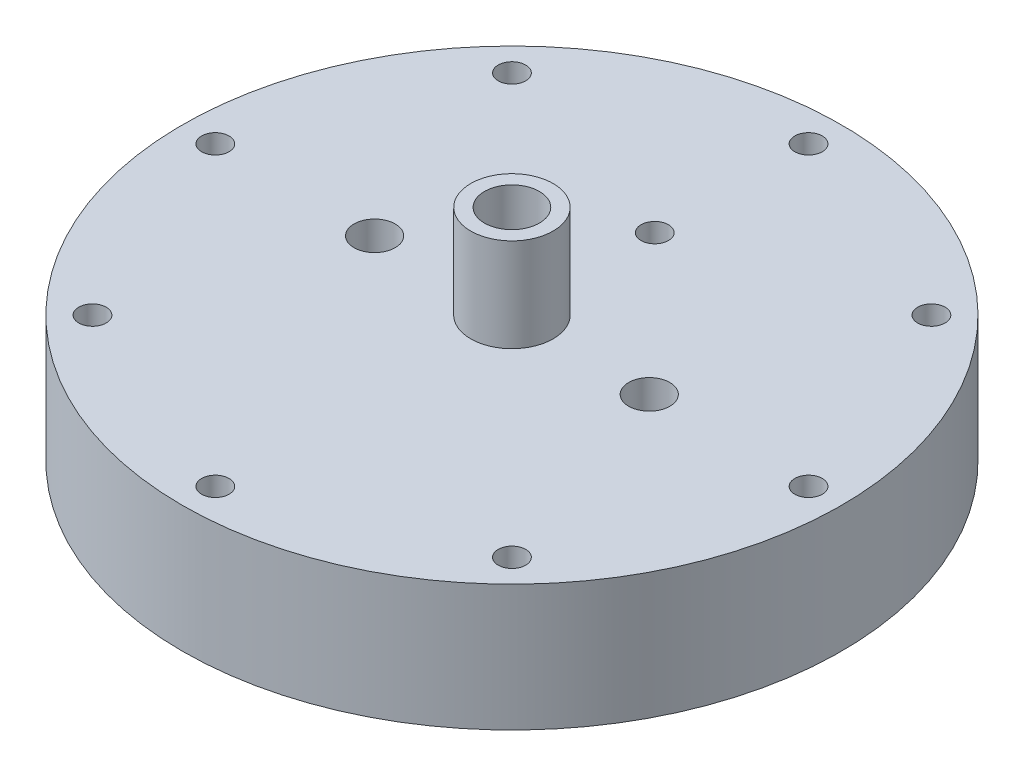
SolidWorks part; units mm, degrees
ref_plane "Front Plane" through (0, 0, 0) normal (0, 0, 1) x (1, 0, 0)
ref_plane "Top Plane" through (0, 0, 0) normal (0, 1, 0) x (1, 0, 0)
ref_plane "Right Plane" through (0, 0, 0) normal (1, 0, 0) x (0, 0, -1)
ref_axis "Axial" through (0, 53.34, 0) along (0, -1, 0)
ref_plane "Bottom Plane" through (0, -50.8, 0) normal (0, 1, 0) x (1, 0, 0)
sketch "Sketch1" plane through (0, 0, 0) normal (0, 1, 0) x (1, 0, 0)
  circle A0 centre (0, 0) radius 76.2
  dimension "D1" = 152.4
extrude "Billet" add sketch "Sketch1" against normal blind 50.8
sketch "Sketch3" plane through (0, -50.8, 0) normal (0, 1, 0) x (1, 0, 0)
  circle A0 centre (0, 0) radius 19.05
  dimension "D1" = 38.1
extrude "Lox Plate" cut sketch "Sketch3" along normal blind 13.97
sketch "Sketch5" plane through (0, -50.8, 0) normal (0, 1, 0) x (1, 0, 0)
  circle A0 centre (0, 0) radius 13.97
  dimension "D1" = 27.94
extrude "Lox Dome" cut sketch "Sketch5" along normal blind 20.32
sketch "Sketch6" plane through (0, -50.8, 0) normal (0, 1, 0) x (1, 0, 0)
  circle A0 centre (0, 0) radius 6.35
  dimension "D1" = 12.7
extrude "Lox Inlet" cut sketch "Sketch6" along normal blind 50.8
sketch "Sketch11" plane through (0, -50.8, 0) normal (0, 1, 0) x (1, 0, 0)
  line L0 (0, 82.3071) -> (0, -82.946) construction
  circle A0 centre (0, 68.58) radius 3.175
  dimension "D1" = 6.35
  dimension "D2" = 68.58
extrude "1/4\" Bolt Hole" cut sketch "Sketch11" along normal up to next
pattern_circular "Bolt Pattern" count 8 over 360 about axis through (0, 53.34, 0) along (0, -1, 0) of "1/4\" Bolt Hole"
sketch "Sketch7" plane through (0, 0, 0) normal (0, 1, 0) x (1, 0, 0)
  circle A0 centre (0, 0) radius 9.525
  circle A1 centre (0, 0) radius 76.2
  dimension "D1" = 19.05
  dimension "D2" = 152.4
extrude "Top Mill" cut sketch "Sketch7" against normal blind 21.59
sketch "Sketch12" plane through (0, -50.8, 0) normal (0, 1, 0) x (1, 0, 0)
  circle A0 centre (0, 0) radius 57.15
extrude "Kerosene Plate" cut sketch "Sketch12" along normal blind 10.16
sketch "Sketch13" plane through (0, 0, 0) normal (0, 1, 0) x (1, 0, 0)
  line L0 (-57.2849, 0) -> (80.0711, 0) construction
  line L1 (0, 48.6602) -> (0, -50.5768) construction
  circle A0 centre (-31.75, 0) radius 4.7625
  circle A1 centre (31.75, 0) radius 4.7625
  dimension "D1" = 9.525
  dimension "D2" = 31.75
extrude "Kerosene Inlet" cut sketch "Sketch13" against normal up to next
sketch "Sketch14" plane through (0, 0, 0) normal (0, 1, 0) x (1, 0, 0)
  line L0 (0, 82.1507) -> (0, -86.6258) construction
  circle A0 centre (0, 33.02) radius 3.175
  dimension "D1" = 6.35
  dimension "D2" = 33.02
extrude "Manifold hole" cut sketch "Sketch14" against normal up to next
sketch "Sketch15" plane through (0, -50.8, 0) normal (0, 1, 0) x (1, 0, 0)
  line L0 (0, 72.5611) -> (0, -49.1199) construction
  circle A0 centre (0, 33.02) radius 7.62
  circle A1 centre (0, 33.02) radius 10.16
  dimension "D1" = 15.24
  dimension "D2" = 20.32
extrude "Manifold seal" cut sketch "Sketch15" along normal blind 12.192
sketch "Sketch16" plane through (0, -50.8, 0) normal (0, 1, 0) x (1, 0, 0)
  circle A0 centre (0, 0) radius 16.51
  circle A1 centre (0, 0) radius 17.78
  dimension "D1" = 33.02
  dimension "D2" = 35.56
extrude "Lox seal" cut sketch "Sketch16" along normal blind 16.002
